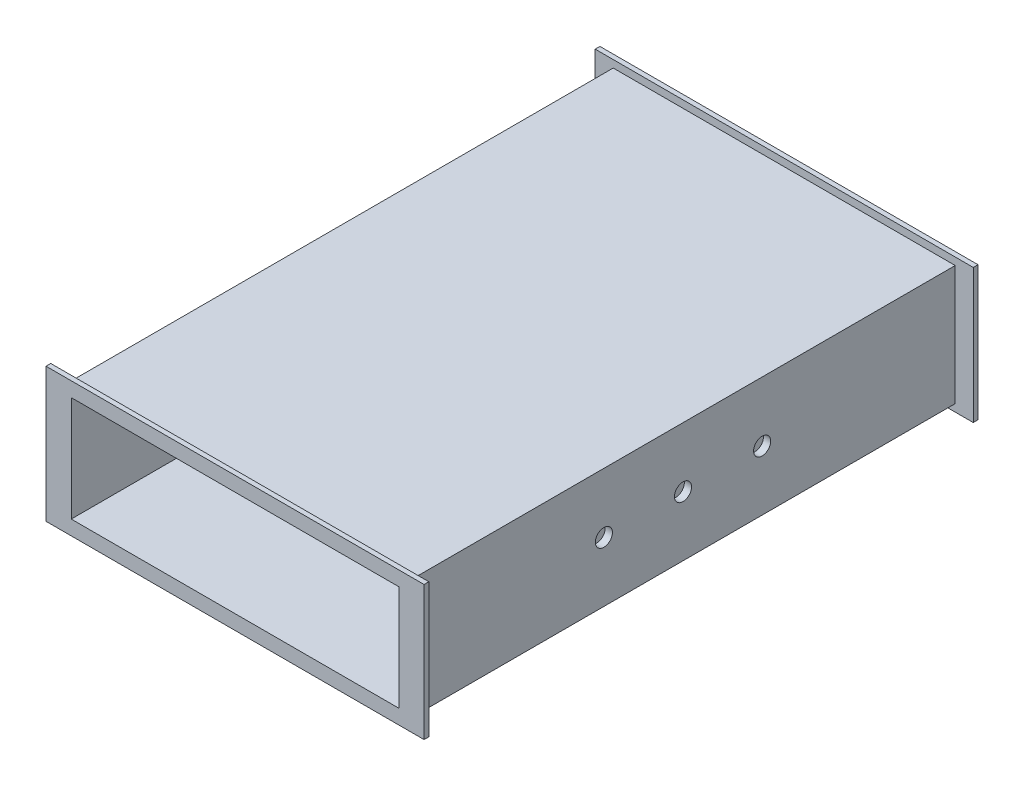
SolidWorks part; units mm, degrees
ref_plane "Front Plane" through (0, 0, 0) normal (0, 0, 1) x (1, 0, 0)
ref_plane "Top Plane" through (0, 0, 0) normal (0, 1, 0) x (1, 0, 0)
ref_plane "Right Plane" through (0, 0, 0) normal (1, 0, 0) x (0, 0, -1)
sketch "Sketch4" plane through (0, 0, 0) normal (0, 0, 1) x (1, 0, 0)
  line L1 (0, 0) -> (200, 0)
  line L2 (0, 0) -> (0, 46)
  line L3 (0, 46) -> (200, 46)
  line L4 (200, 0) -> (200, 46)
extrude "Boss-Extrude3" add sketch "Sketch4" along normal blind 150
ref_plane "Plane1" through (0, 0, 250) normal (0, 0, 1) x (1, 0, 0)
ref_plane "Plane2" through (0, 0, -100) normal (0, 0, -1) x (-1, 0, 0)
sketch "Sketch6" plane through (0, 0, 250) normal (0, 0, 1) x (1, 0, 0)
  line L7 (-19.4454, 65.4454) -> (-19.4454, -19.4454)
  line L10 (-19.4454, -19.4454) -> (219.4454, -19.4454)
  line L12 (219.4454, -19.4454) -> (219.4454, 65.4454)
  line L13 (-19.4454, 65.4454) -> (219.4454, 65.4454)
extrude "Boss-Extrude5" add sketch "Sketch6" against normal blind 3 separate body
sketch "Sketch7" plane through (0, 0, 250) normal (0, 0, 1) x (1, 0, 0)
  line L4 (-3.4898, 56.2335) -> (203.4898, 56.2335)
  line L5 (203.4898, 56.2335) -> (203.4898, -10.2335)
  line L6 (203.4898, -10.2335) -> (-3.4898, -10.2335)
  line L7 (-3.4898, 56.2335) -> (-3.4898, -10.2335)
extrude "Cut-Extrude1" cut sketch "Sketch7" against normal blind 3
sketch "Sketch8" plane through (0, 0, -100) normal (0, 0, -1) x (-1, 0, 0)
  line L1 (-219.4454, 65.4454) -> (19.4454, 65.4454)
  line L2 (-219.4454, 65.4454) -> (-219.4454, -19.4454)
  line L3 (-219.4454, -19.4454) -> (19.4454, -19.4454)
  line L4 (19.4454, 65.4454) -> (19.4454, -19.4454)
extrude "Boss-Extrude6" add sketch "Sketch8" against normal blind 3 separate body
sketch "Sketch9" plane through (0, 0, -100) normal (0, 0, -1) x (-1, 0, 0)
  line L4 (-203.4898, 56.2335) -> (3.4898, 56.2335)
  line L5 (3.4898, 56.2335) -> (3.4898, -10.2335)
  line L6 (-203.4898, -10.2335) -> (-203.4898, 56.2335)
  line L7 (-203.4898, -10.2335) -> (3.4898, -10.2335)
extrude "Cut-Extrude2" cut sketch "Sketch9" against normal blind 3
sketch "Sketch10" plane through (0, 0, -97) normal (0, 0, 1) x (1, 0, 0)
  line L0 (-3.4898, 56.2335) -> (203.4898, 56.2335)
  line L1 (203.4898, 56.2335) -> (203.4898, -10.2335)
  line L2 (203.4898, -10.2335) -> (-3.4898, -10.2335)
  line L3 (-3.4898, -10.2335) -> (-3.4898, 56.2335)
  line L4 (208.0512, -14.7948) -> (208.0512, 60.7948)
  line L5 (208.0512, 60.7948) -> (-8.0512, 60.7948)
  line L6 (-8.0512, 60.7948) -> (-8.0512, -14.7948)
  line L7 (-8.0512, -14.7948) -> (208.0512, -14.7948)
extrude "Boss-Extrude7" add sketch "Sketch10" along normal up to surface (344 mm away) up to face at (100, 23, 247)
sketch "Sketch14" plane through (-8.0512, 0, 0) normal (-1, 0, 0) x (0, 0, 1)
  line L0 (75, 60.7948) -> (75, -14.7948) construction
  line L1 (247, 60.7948) -> (-97, 60.7948) construction
  line L2 (247, -14.7948) -> (-97, -14.7948) construction
  circle A0 centre (75, 23) radius 5.4
  circle A1 centre (125, 23) radius 5.4
  circle A2 centre (25, 23) radius 5.4
  dimension "D1" = 2
  dimension "D2" = 2
extrude "Cut-Extrude4" cut sketch "Sketch14" against normal through all both and the other way through all
